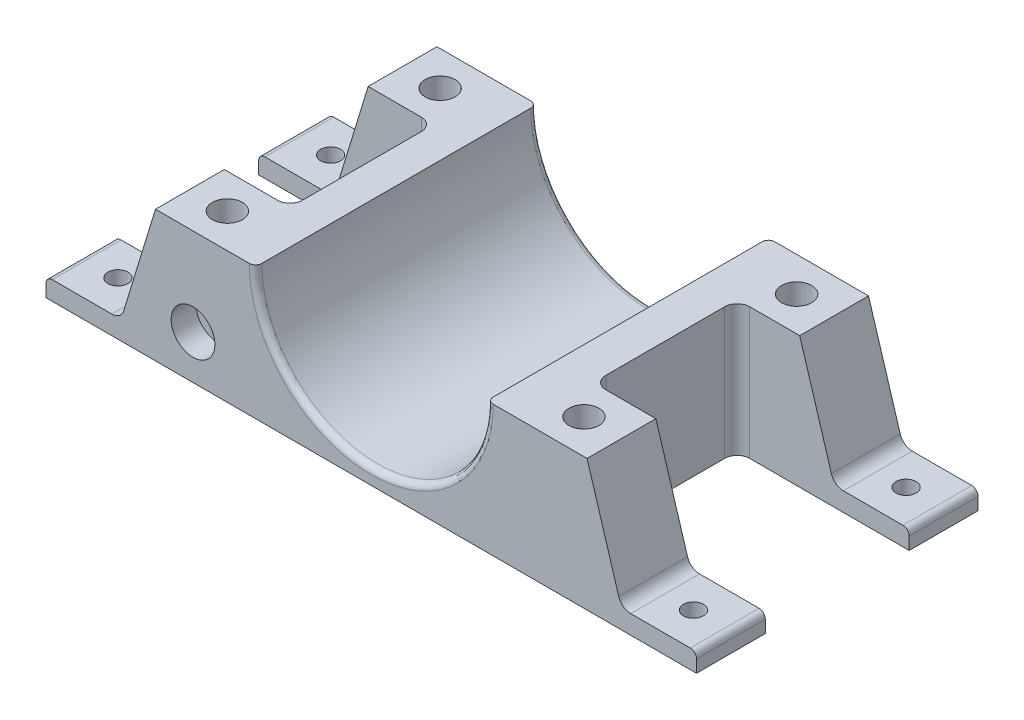
SolidWorks part; units mm, degrees
material "PETG - Polymaker"
ref_plane "Front Plane" through (0, 0, 0) normal (0, 0, 1) x (1, 0, 0)
ref_plane "Top Plane" through (0, 0, 0) normal (0, 1, 0) x (1, 0, 0)
ref_plane "Right Plane" through (0, 0, 0) normal (1, 0, 0) x (0, 0, -1)
sketch "Sketch1" plane through (0, 0, 0) normal (0, 0, 1) x (1, 0, 0)
  line L0 (0, 0) -> (50000, 0) construction
  line L1 (0, 0) -> (0, 50000) construction
  line L2 (-18.5, 0) -> (-34.5, 0)
  line L3 (-34.5, 0) -> (-40, -18)
  line L4 (-40, -18) -> (-52, -18)
  line L5 (-52, -18) -> (-52, -21)
  line L6 (-52, -21) -> (0, -21)
  line L7 (0, -18.5) -> (50000, -18.5) construction
  line L8 (18.5, 0) -> (34.5, 0)
  line L9 (34.5, 0) -> (40, -18)
  line L10 (40, -18) -> (52, -18)
  line L11 (52, -18) -> (52, -21)
  line L12 (52, -21) -> (0, -21)
  circle A0 centre (0, 0) radius 18 construction
  arc A1 (-18.5, 0) -> (18.5, 0) centre (0, 0) ccw
  point P16 (0, -18.5)
  dimension "D1" = 36
  dimension "D2" = 0.5
  dimension "D3" = 16
  dimension "D4" = 12
  dimension "D5" = 2.5
  dimension "D6" = 18
  dimension "D7" = 52
  dimension "D8" = 12
  dimension "D9" = 16
  dimension "50" = 52
  dimension "D10" = 18
extrude "Boss-Extrude1" add sketch "Sketch1" along normal mid plane 45
sketch "Sketch2" plane through (0, 0, 0) normal (0, 1, 0) x (1, 0, 0)
  line L0 (-65, 0) -> (-50065, 0) construction
  line L1 (-52, -22.5) -> (-52, 22.5) construction
  line L2 (-24, -11.5) -> (-24, 11.5)
  line L3 (-34.5, -22.5) -> (-34.5, 22.5) construction
  line L4 (-52, -11.5) -> (-52, 11.5)
  line L5 (-24, 11.5) -> (-52, 11.5)
  line L6 (-40, 22.5) -> (-52, 22.5) construction
  line L7 (-24, -11.5) -> (-52, -11.5)
  line L8 (52, -22.5) -> (52, 22.5) construction
  line L9 (52, -11.5) -> (52, 11.5)
  line L10 (52, -11.5) -> (52, 11.5)
  line L11 (52, 11.5) -> (24.5, 11.5)
  line L13 (24.5, 11.5) -> (24.5, -11.5)
  line L14 (52, -11.5) -> (24.5, -11.5)
  line L15 (52, 22.5) -> (40, 22.5) construction
  line L16 (-18.5, -22.5) -> (-18.5, 22.5) construction
  line L19 (18.5, -22.5) -> (18.5, 22.5) construction
  point P4 (-52, 0)
  point P10 (-34.5, 0)
  point P15 (-52, 0)
  point P24 (24.5, 0)
  point P25 (52, 0)
  line M8 (-34.5, 22.5) -> (-34.5, -22.5)
  dimension "D1" = 11
  dimension "D2" = 11
  dimension "D3" = 5.5
  dimension "D4" = 6
extrude "Cut-Extrude1" cut sketch "Sketch2" against normal blind 65 contours L2 L0 L4 L7 | L0 L5 L4 M8 | L0 L10 L11 L13 | L9 L0 L13 L14 | L7 L4 L5 L2 | L13 L14 L10 L11 region at (-43.25, 0, 0) region at (38.25, 0, 0)
sketch "Sketch3" plane through (0, -18, 0) normal (0, 1, 0) x (1, 0, 0)
  line L0 (-60, 17) -> (-50060, 17) construction
  line L1 (-52, 11.5) -> (-52, 22.5) construction
  line L2 (-46, 22.5) -> (-46, 50022.5) construction
  line L3 (-40, 22.5) -> (-52, 22.5) construction
  line L4 (0, 0) -> (50000, 0) construction
  line L5 (46, 22.5) -> (46, 50022.5) construction
  line L6 (52, 22.5) -> (40, 22.5) construction
  circle A0 centre (-46, 17) radius 1.6
  circle A1 centre (46, 17) radius 1.6
  circle A2 centre (46, -17) radius 1.6
  circle A3 centre (-46, -17) radius 1.6
  point P4 (-52, 17)
  point P9 (-46, 22.5)
  point P17 (46, 22.5)
  dimension "D1" = 3.2
  dimension "D2" = 3.2
  dimension "D3" = 92
  dimension "D4" = 34
extrude "Cut-Extrude2" cut sketch "Sketch3" against normal blind 65
sketch "Sketch4" plane through (0, 0, 22.5) normal (0, 0, 1) x (1, 0, 0)
  line L0 (-52, -21) -> (52, -21) construction
  circle A0 centre (-28.5, -14) radius 3.5
  dimension "D2" = 7
  dimension "D1" = 10
  dimension "D3" = 7
extrude "Bearing-Hole" cut sketch "Sketch4" against normal blind 4
mirror "Mirror1" about plane through (0, 0, 0) normal (0, 0, 1) of "Bearing-Hole"
sketch "Sketch5" plane through (0, 0, 18.5) normal (0, 0, 1) x (1, 0, 0)
  line L0 (-28.5, -9.3202) -> (-28.5, 49990.6798) construction
  line L1 (-31.3186, -14) -> (49968.6814, -14) construction
  line L2 (-25, -14) -> (-32, -14) construction
  line L3 (-32, -8.25) -> (-32, 49991.75) construction
  line L4 (-35.25, -10.5) -> (49964.75, -10.5) construction
  circle A0 centre (-28.5, -14) radius 1.5
  circle A1 centre (-28.5, -14) radius 3.5 construction
  circle A2 centre (-28.5, -14) radius 3.5 construction
  point P17 (-28.5, -10.5)
  dimension "D1" = 3
extrude "Axle-Thru-Holes" cut sketch "Sketch5" against normal through all both and the other way through all
fillet "Fillet2" radius 1 6 edges at (0, -18.5, -22.5) (0, -18.5, 22.5) (52, -18, -17) (52, -18, 17) (-52, -18, -17) (-52, -18, 17)
fillet "Fillet3" radius 2 4 edges at (24.5, -10.5, -11.5) (24.5, -10.5, 11.5) (-24, -10.5, 11.5) (-24, -10.5, -11.5)
sketch "Sketch6" plane through (0, 0, 0) normal (0, 1, 0) x (1, 0, 0)
  line L0 (-28.5, 22.5) -> (-28.5, -49977.5) construction
  line L2 (0, 0) -> (0, -50000) construction
  line L3 (-33.8123, 17) -> (-49.3072, 17) construction
  line L5 (0, 0) -> (50000, 0) construction
  line L6 (-18.5, -21.5) -> (-18.5, 21.5) construction
  circle A0 centre (-28.5, 17) radius 2.4
  circle A1 centre (28.5, 17) radius 2.4
  circle A2 centre (28.5, -17) radius 2.4
  circle A3 centre (-28.5, -17) radius 2.4
  dimension "D1" = 4.8
  dimension "D2" = 10
extrude "Top-Mount-Holes" cut sketch "Sketch6" against normal blind 7 and the other way through all
fillet "Fillet4" radius 2 4 edges at (40, -18, -17) (40, -18, 17) (-40, -18, 17) (-40, -18, -17)
